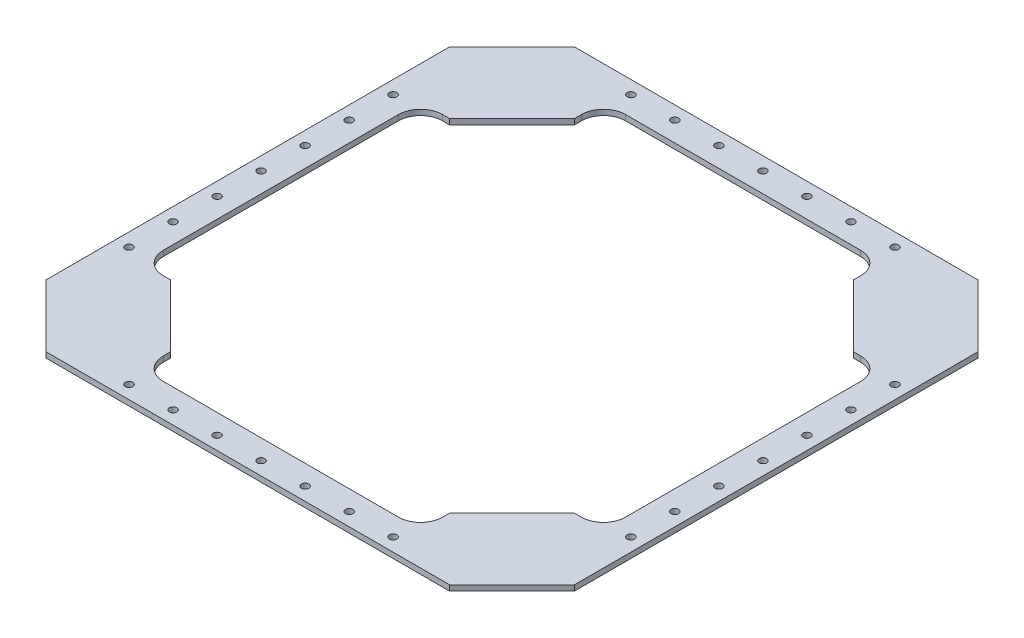
SolidWorks part; units mm, degrees
ref_plane "Front Plane" through (0, 0, 0) normal (0, 0, 1) x (1, 0, 0)
ref_plane "Top Plane" through (0, 0, 0) normal (0, 1, 0) x (1, 0, 0)
ref_plane "Right Plane" through (0, 0, 0) normal (1, 0, 0) x (0, 0, -1)
sketch "Sketch2" plane through (0, 0, 0) normal (0, 1, 0) x (1, 0, 0)
  line L0 (-152.4, 116.479) -> (-116.479, 152.4)
  line L1 (-116.479, 152.4) -> (116.479, 152.4)
  line L2 (-152.4, 116.479) -> (-152.4, -116.479)
  line L3 (-116.479, 80.558) -> (-80.558, 116.479)
  line L4 (-134.4395, 134.4395) -> (-98.5185, 98.5185) construction
  line L5 (-67.858, 133.35) -> (67.858, 133.35)
  line L6 (-133.35, 67.858) -> (-133.35, -67.858)
  line L7 (-116.479, 80.558) -> (-120.65, 80.558)
  line L8 (-80.558, 116.479) -> (-80.558, 120.65)
  line L9 (0, 0) -> (0, 208.1331) construction
  line L10 (0, 0) -> (-190.1851, 0) construction
  line L11 (133.35, 67.858) -> (133.35, -67.858)
  line L12 (152.4, 116.479) -> (152.4, -116.479)
  line L13 (134.4395, 134.4395) -> (98.5185, 98.5185) construction
  line L14 (80.558, 116.479) -> (80.558, 120.65)
  line L15 (116.479, 80.558) -> (120.65, 80.558)
  line L16 (116.479, 80.558) -> (80.558, 116.479)
  line L17 (152.4, 116.479) -> (116.479, 152.4)
  line L18 (134.4395, -134.4395) -> (98.5185, -98.5185) construction
  line L19 (-134.4395, -134.4395) -> (-98.5185, -98.5185) construction
  line L20 (152.4, -116.479) -> (116.479, -152.4)
  line L21 (116.479, -80.558) -> (80.558, -116.479)
  line L22 (116.479, -80.558) -> (120.65, -80.558)
  line L23 (80.558, -116.479) -> (80.558, -120.65)
  line L24 (-80.558, -116.479) -> (-80.558, -120.65)
  line L25 (-116.479, -80.558) -> (-120.65, -80.558)
  line L26 (-67.858, -133.35) -> (67.858, -133.35)
  line L27 (-116.479, -80.558) -> (-80.558, -116.479)
  line L28 (-116.479, -152.4) -> (116.479, -152.4)
  line L29 (-152.4, -116.479) -> (-116.479, -152.4)
  arc A0 (-80.558, 120.65) -> (-67.858, 133.35) centre (-67.858, 120.65) cw
  arc A1 (-120.65, 80.558) -> (-133.35, 67.858) centre (-120.65, 67.858) ccw
  arc A2 (120.65, 80.558) -> (133.35, 67.858) centre (120.65, 67.858) cw
  arc A3 (80.558, 120.65) -> (67.858, 133.35) centre (67.858, 120.65) ccw
  arc A4 (80.558, -120.65) -> (67.858, -133.35) centre (67.858, -120.65) cw
  arc A5 (120.65, -80.558) -> (133.35, -67.858) centre (120.65, -67.858) ccw
  arc A6 (-120.65, -80.558) -> (-133.35, -67.858) centre (-120.65, -67.858) cw
  arc A7 (-80.558, -120.65) -> (-67.858, -133.35) centre (-67.858, -120.65) ccw
  point P23 (133.35, 0)
  point P25 (0, 133.35)
  point P26 (0, 152.4)
  point P54 (152.4, 0)
  point P56 (-133.35, 0)
  point P57 (-152.4, 0)
  point P58 (0, -152.4)
  point P59 (0, -133.35)
  dimension "D10" = 12.7
  dimension "D1" = 50.8
  dimension "D2" = 152.4
  dimension "D3" = 152.4
  dimension "D4" = 50.8
  dimension "D5" = 19.05
  dimension "D6" = 19.05
  dimension "D7" = 45
  dimension "D8" = 45
  dimension "D9" = 50.8
extrude "Boss-Extrude1" add sketch "Sketch2" along normal blind 3.175
sketch "Sketch3" plane through (0, 3.175, 0) normal (0, 1, 0) x (1, 0, 0)
  line L0 (0, 245.5474) -> (0, -200.3002) construction
  line L1 (-185.3968, 0) -> (177.6158, 0) construction
  line L2 (116.479, 152.4) -> (-116.479, 152.4) construction
  line L3 (-152.4, 116.479) -> (-152.4, -116.479) construction
  line L4 (0, -245.5474) -> (0, 200.3002) construction
  circle A0 centre (-25.4, 144.78) radius 2.159
  circle A1 centre (-76.2, 144.78) radius 2.159
  circle A2 centre (-144.78, 76.2) radius 2.159
  circle A3 centre (-144.78, 25.4) radius 2.159
  circle A4 centre (144.78, 25.4) radius 2.159
  circle A5 centre (144.78, 76.2) radius 2.159
  circle A6 centre (25.4, 144.78) radius 2.159
  circle A7 centre (76.2, 144.78) radius 2.159
  circle A8 centre (76.2, -144.78) radius 2.159
  circle A9 centre (25.4, -144.78) radius 2.159
  circle A10 centre (144.78, -76.2) radius 2.159
  circle A11 centre (144.78, -25.4) radius 2.159
  circle A12 centre (-144.78, -25.4) radius 2.159
  circle A13 centre (-144.78, -76.2) radius 2.159
  circle A14 centre (-76.2, -144.78) radius 2.159
  circle A15 centre (-25.4, -144.78) radius 2.159
  dimension "D3" = 4.318
  dimension "D4" = 4.318
  dimension "D7" = 4.318
  dimension "D8" = 4.318
  dimension "D10" = 25.4
  dimension "D1" = 50.8
  dimension "D2" = 25.4
  dimension "D5" = 7.62
  dimension "D6" = 7.62
  dimension "D9" = 50.8
  dimension "D11" = 7.62
  dimension "D12" = 7.62
extrude "Cut-Extrude1" cut sketch "Sketch3" against normal through all
sketch "Sketch4" plane through (0, 3.175, 0) normal (0, 1, 0) x (1, 0, 0)
  line L0 (0, 201.0925) -> (0, -226.4518) construction
  line L1 (-181.7718, 0) -> (192.408, 0) construction
  line L2 (116.479, 152.4) -> (-116.479, 152.4) construction
  line L3 (-152.4, 116.479) -> (-152.4, -116.479) construction
  circle A0 centre (0, 144.78) radius 2.159
  circle A1 centre (-50.8, 144.78) radius 2.159
  circle A2 centre (-144.78, 50.8) radius 2.159
  circle A3 centre (-144.78, 0) radius 2.159
  circle A4 centre (144.78, 0) radius 2.159
  circle A5 centre (144.78, 50.8) radius 2.159
  circle A6 centre (50.8, 144.78) radius 2.159
  circle A7 centre (50.8, -144.78) radius 2.159
  circle A8 centre (144.78, -50.8) radius 2.159
  circle A9 centre (-50.8, -144.78) radius 2.159
  circle A10 centre (0, -144.78) radius 2.159
  circle A11 centre (-144.78, -50.8) radius 2.159
  dimension "D1" = 4.318
  dimension "D2" = 4.318
  dimension "D3" = 4.318
  dimension "D4" = 4.318
  dimension "D5" = 7.62
  dimension "D6" = 7.62
  dimension "D7" = 50.8
  dimension "D8" = 7.62
  dimension "D9" = 7.62
  dimension "D10" = 50.8
extrude "Cut-Extrude2" cut sketch "Sketch4" against normal through all
